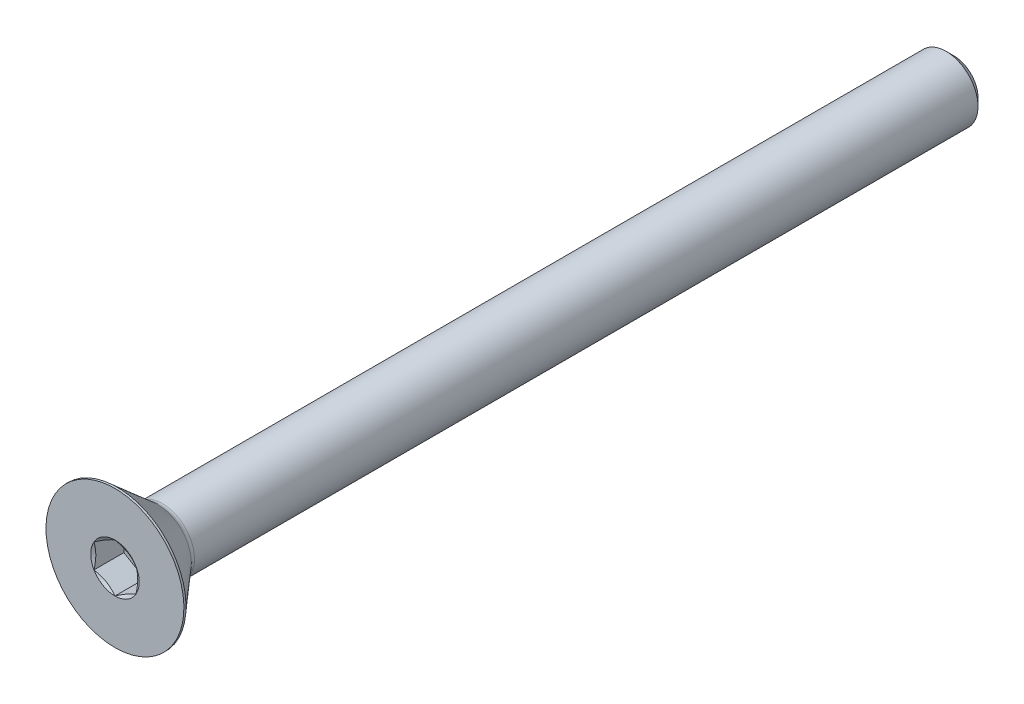
SolidWorks part; units mm, degrees
material "Plain Carbon Steel"
ref_plane "Front" through (0, 0, 0) normal (0, 0, 1) x (1, 0, 0)
ref_plane "Top" through (0, 0, 0) normal (0, 1, 0) x (1, 0, 0)
ref_plane "Right" through (0, 0, 0) normal (1, 0, 0) x (0, 0, -1)
sketch "Sketch1" plane through (0, 0, 0) normal (1, 0, 0) x (0, 0, -1)
  line L0 (0, 5.2197) -> (0.1613, 5.2197) construction
  line L1 (0.1613, 5.2197) -> (3.2258, 2.5558) construction
  line L2 (0, 2.413) -> (63.5, 2.413)
  line L3 (63.5, 2.413) -> (63.5, 0)
  line L4 (63.5, 0) -> (0, 0)
  line L5 (0, 0) -> (0, 5.2197) construction
  line L6 (0, 5.2197) -> (0, -5.2197) construction
  line L7 (63.5, 2.413) -> (63.5, -2.413) construction
  line L8 (0, -5.2197) -> (0.1613, -5.2197) construction
  line L9 (0.1613, -5.2197) -> (3.2258, -2.5558) construction
  line L11 (0, 2.413) -> (0, 0)
  line L12 (3.6076, 2.413) -> (3.6076, 0) construction
  line L13 (38.1, 0) -> (38.1, 2.413) construction
  arc A1 (3.2258, 2.5558) -> (3.6076, 2.413) centre (3.6076, 2.995) ccw construction
  dimension "D1" = 0.1613
  dimension "Min Thread" = 25.4
revolve "Revolve1" add sketch "Sketch1" angle 360 mid plane about L4
ref_plane "Plane2" through (0, 0, -38.1) normal (0, 0, 1) x (1, 0, 0)
chamfer "Chamfer1" distance 0.5953 angle 45 1 edges at (0, 2.413, -63.5)
sketch "Sketch7" plane through (0, 0, 0) normal (1, 0, 0) x (0, 0, -1)
  line L0 (0, 5.2197) -> (0.1613, 5.2197) construction
  line L1 (0.1613, 5.2197) -> (3.2258, 2.5558) construction
  line L2 (0, 5.2197) -> (0.1613, 5.2197)
  line L3 (0.1613, 5.2197) -> (3.2258, 2.5558)
  line L4 (3.6076, 2.413) -> (3.6076, 0) construction
  line L5 (3.6076, 2.413) -> (3.6076, 0)
  line L7 (0, 0) -> (0, 5.2197) construction
  line L8 (0, 0) -> (0, 5.2197)
  line L9 (0, 0) -> (3.6076, 0)
  line L10 (5.7417, 0) -> (-5.7417, 0) construction
  arc A0 (3.2258, 2.5558) -> (3.6076, 2.413) centre (3.6076, 2.995) ccw construction
  arc A1 (3.2258, 2.5558) -> (3.6076, 2.413) centre (3.6076, 2.995) ccw
revolve "Revolve2" add sketch "Sketch7" angle 360 mid plane about L9
ref_plane "Plane1" through (0, 0, -3.6076) normal (0, 0, 1) x (1, 0, 0)
sketch "Sketch5" plane through (0, 0, 0) normal (0, 0, 1) x (1, 0, 0)
  line L0 (0, 0) -> (-1.8331, 0) construction
  line L1 (0, 0) -> (-2.7496, 1.5875) construction
  line L2 (0, 0) -> (-2.7496, -1.5875) construction
  line L6 (0, 1.8331) -> (0, 1.5119) construction
  line L7 (0, 1.5119) -> (0, 1.1906) construction
  line L9 (0, 1.8331) -> (-1.5875, 0.9165)
  line L10 (-1.5875, 0.9165) -> (-1.5875, -0.9165)
  line L11 (-1.5875, -0.9165) -> (0, -1.8331)
  line L12 (0, -1.8331) -> (1.5875, -0.9165)
  line L13 (1.5875, -0.9165) -> (1.5875, 0.9165)
  line L14 (1.5875, 0.9165) -> (0, 1.8331)
  circle A0 centre (0, 0) radius 1.8331 construction
  circle A1 centre (0, 0) radius 1.5119 construction
  circle A2 centre (0, 0) radius 1.1906 construction
  circle A3 centre (0, 0) radius 1.5875 construction
  dimension "D3" = 2.3813
  dimension "D4" = 30
  dimension "D5" = 30
extrude "Cut-Extrude2" cut sketch "Sketch5" against normal blind 2.2581
sketch "Sketch6" plane through (0, 0, 0) normal (0, 0, 1) x (1, 0, 0)
  circle A0 centre (0, 0) radius 1.8331
extrude "Cut-Extrude3" cut sketch "Sketch6" against normal blind 2.2581 draft 60
sketch "Sketch9" [suppressed] plane through (0, 0, -3.6076) normal (0, 0, 1) x (1, 0, 0)
  circle A1 centre (0, 0) radius 2.413
  circle A2 centre (0, 0) radius 2.413
  point P0 (0, 2.413)
  dimension "D1" = 0
extrude "Boss-Extrude2" [suppressed] add sketch "Sketch9" against normal up to surface (15.4424 mm away) up to plane "Plane2"
move or copy body "Body-Move/Copy1" [suppressed] bodies to move or copy 113
equation "\"D1@Cut-Extrude2\" = \"Head Ht@Sketch1\" * .7"
equation "\"D1@Sketch1\" = \"Head Ht@Sketch1\" * .05"
equation "\"D1@Cut-Extrude3\" = \"D1@Cut-Extrude2\""
equation "\"D3@Sketch5\" = \"Hex@Sketch5\" * .75"
